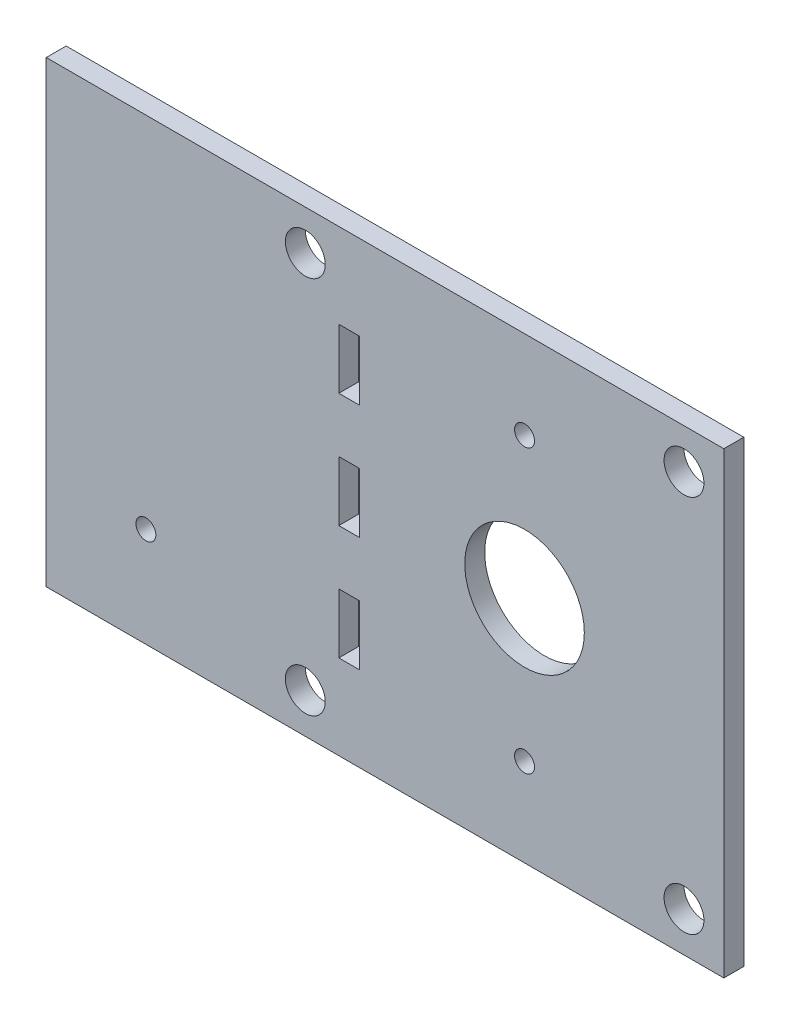
SolidWorks part; units mm, degrees
ref_plane "Front Plane" through (0, 0, 0) normal (0, 0, 1) x (1, 0, 0)
ref_plane "Top Plane" through (0, 0, 0) normal (0, 1, 0) x (1, 0, 0)
ref_plane "Right Plane" through (0, 0, 0) normal (1, 0, 0) x (0, 0, -1)
sketch "Sketch1" plane through (0, 0, 0) normal (0, 0, 1) x (1, 0, 0)
  line L0 (0, 73.025) -> (0, -73.025) construction
  line L1 (63.5, 73.025) -> (-152.4, 73.025)
  line L2 (63.5, 73.025) -> (63.5, -73.025)
  line L3 (63.5, -73.025) -> (-152.4, -73.025)
  line L4 (-152.4, 73.025) -> (-152.4, -73.025)
  line L5 (0, 45) -> (0, -45) construction
  line L6 (-55.88, 73.025) -> (-55.88, 36.5125) construction
  line L7 (-59.182, -9.525) -> (-52.578, -9.525)
  line L8 (-59.182, -9.525) -> (-59.182, 9.525)
  line L9 (-59.182, 9.525) -> (-52.578, 9.525)
  line L10 (-52.578, -9.525) -> (-52.578, 9.525)
  line L11 (-59.182, -9.525) -> (-52.578, 9.525) construction
  line L12 (-59.182, 9.525) -> (-52.578, -9.525) construction
  line L13 (-59.182, 46.0375) -> (-52.578, 46.0375)
  line L14 (-59.182, 46.0375) -> (-59.182, 26.9875)
  line L15 (-59.182, 26.9875) -> (-52.578, 26.9875)
  line L16 (-52.578, 46.0375) -> (-52.578, 26.9875)
  line L17 (-59.182, 46.0375) -> (-52.578, 26.9875) construction
  line L18 (-59.182, 26.9875) -> (-52.578, 46.0375) construction
  line L19 (-59.182, -26.9875) -> (-52.578, -26.9875)
  line L20 (-59.182, -26.9875) -> (-59.182, -46.0375)
  line L21 (-59.182, -46.0375) -> (-52.578, -46.0375)
  line L22 (-52.578, -26.9875) -> (-52.578, -46.0375)
  line L23 (-59.182, -26.9875) -> (-52.578, -46.0375) construction
  line L24 (-59.182, -46.0375) -> (-52.578, -26.9875) construction
  line L25 (-55.88, 36.5125) -> (-55.88, 0) construction
  line L26 (-55.88, 0) -> (-55.88, -36.5125) construction
  line L27 (-55.88, -36.5125) -> (-55.88, -73.025) construction
  circle A0 centre (50.8, 60.325) radius 6.35
  circle A1 centre (50.8, -60.325) radius 6.35
  circle A2 centre (0, 0) radius 19.05
  circle A3 centre (0, 45) radius 3.175
  circle A4 centre (0, -45) radius 3.175
  circle A5 centre (-69.85, 60.325) radius 6.35
  circle A6 centre (-69.85, -60.325) radius 6.35
  point P0 (0, 0)
  point P14 (0, 0)
  point P19 (0, 0)
  point P24 (-55.88, 36.5125)
  point P28 (-55.88, 0)
  point P34 (-55.88, -36.5125)
  dimension "D2" = 12.7
  dimension "D6" = 38.1
  dimension "D8" = 6.35
  dimension "D1" = 146.05
  dimension "D3" = 12.7
  dimension "D4" = 12.7
  dimension "D5" = 50.8
  dimension "D7" = 90
  dimension "D9" = 12.7
  dimension "D10" = 152.4
  dimension "D11" = 69.85
  dimension "D12" = 19.05
  dimension "D13" = 6.604
  dimension "D14" = 55.88
extrude "Boss-Extrude1" add sketch "Sketch1" along normal mid plane 6.35
sketch "Sketch2" plane through (0, 0, 3.175) normal (0, 0, 1) x (1, 0, 0)
  line L0 (-152.4, -73.025) -> (63.5, -73.025) construction
  line L1 (-152.4, 73.025) -> (-152.4, -73.025) construction
  circle A0 centre (-120.65, -41.275) radius 3.175
  dimension "D1" = 6.35
  dimension "D2" = 31.75
  dimension "D3" = 31.75
extrude "Cut-Extrude1" cut sketch "Sketch2" against normal through all
